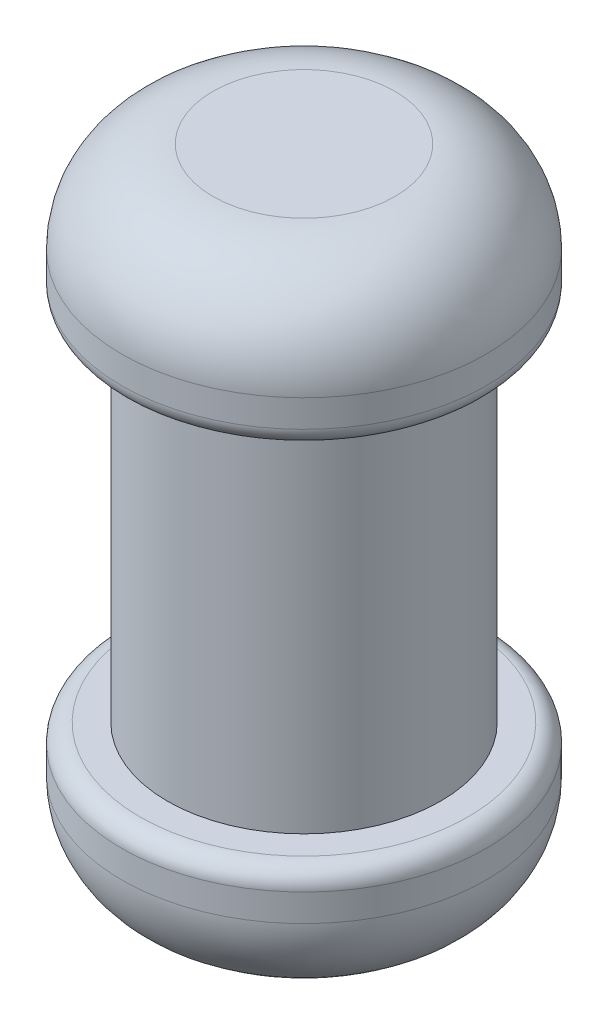
SolidWorks part; units mm, degrees
ref_plane "Front Plane" through (0, 0, 0) normal (0, 0, 1) x (1, 0, 0)
ref_plane "Top Plane" through (0, 0, 0) normal (0, 1, 0) x (1, 0, 0)
ref_plane "Right Plane" through (0, 0, 0) normal (1, 0, 0) x (0, 0, -1)
sketch "Sketch1" plane through (0, 0, 0) normal (0, 1, 0) x (1, 0, 0)
  circle A0 centre (0, 0) radius 1.5
  dimension "D1" = 3
extrude "Boss-Extrude1" add sketch "Sketch1" along normal blind 2
sketch "Sketch2" plane through (0, 2, 0) normal (0, 1, 0) x (1, 0, 0)
  circle A0 centre (0, 0) radius 2
extrude "Boss-Extrude2" add sketch "Sketch2" along normal blind 1.5
fillet "Fillet1" radius 1 1 edges at (0, 3.5, 2)
fillet "Fillet2" radius 0.2 1 edges at (0, 2, 2)
mirror "Mirror2" about plane through (0, 0, 0) normal (0, 1, 0) of "Fillet1", "Fillet2", "Boss-Extrude2", "Boss-Extrude1"
